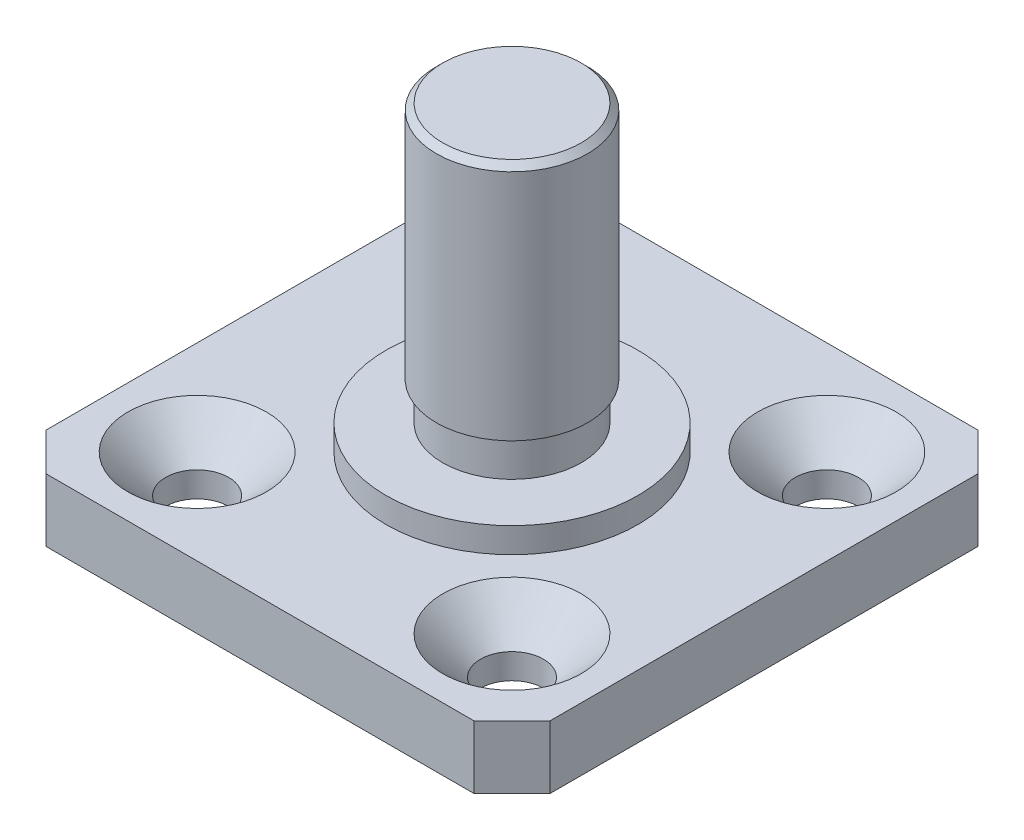
SolidWorks part; units mm, degrees
material "Литая углеродистая сталь"
ref_plane "Спереди" through (0, 0, 0) normal (0, 0, 1) x (1, 0, 0)
ref_plane "Сверху" through (0, 0, 0) normal (0, 1, 0) x (1, 0, 0)
ref_plane "Справа" through (0, 0, 0) normal (1, 0, 0) x (0, 0, -1)
sketch "Эскиз1" plane through (0, 0, 0) normal (0, 1, 0) x (1, 0, 0)
  line L1 (-20, -20) -> (20, -20)
  line L2 (-20, -20) -> (-20, 20)
  line L3 (-20, 20) -> (20, 20)
  line L4 (20, -20) -> (20, 20)
  line L5 (0, 20) -> (0, -20) construction
  line L6 (-20, 0) -> (20, 0) construction
  point P0 (0, 0)
  dimension "D1" = 40
extrude "Бобышка-Вытянуть1" add sketch "Эскиз1" along normal blind 5
chamfer "Фаска1" distance 3 angle 45 4 edges at (-20, 2.5, -20) (20, 2.5, -20) (-20, 2.5, 20) (20, 2.5, 20)
sketch "Эскиз2" plane through (0, 5, 0) normal (0, 1, 0) x (1, 0, 0)
  circle A0 centre (0, 0) radius 10
  dimension "D1" = 20
extrude "Бобышка-Вытянуть2" add sketch "Эскиз2" along normal blind 2
sketch "Эскиз3" plane through (0, 7, 0) normal (0, 1, 0) x (1, 0, 0)
  circle A0 centre (0, 0) radius 6
  dimension "D1" = 12
extrude "Бобышка-Вытянуть3" add sketch "Эскиз3" along normal blind 22
sketch "Эскиз4" plane through (0, 7, 0) normal (0, 1, 0) x (1, 0, 0)
  circle A0 centre (0, 0) radius 6 construction
  circle A1 centre (0, 0) radius 6
  circle A4 centre (0, 0) radius 5.5
  circle A5 centre (0, 0) radius 5.5
  dimension "D1" = 0.5
extrude "Вырез-Вытянуть1" cut sketch "Эскиз4" along normal blind 3
sketch "Эскиз5" plane through (0, 5, 0) normal (0, 1, 0) x (1, 0, 0)
  line L0 (0, 0) -> (0, 8.071) construction
  line L1 (0, 0) -> (4.4681, 0) construction
  circle A0 centre (-12.5, 12.5) radius 2.5
  circle A1 centre (12.5, 12.5) radius 2.5
  circle A2 centre (12.5, -12.5) radius 2.5
  circle A3 centre (-12.5, -12.5) radius 2.5
  dimension "D1" = 5
  dimension "D2" = 25
  dimension "D3" = 25
extrude "Вырез-Вытянуть2" cut sketch "Эскиз5" against normal through all
chamfer "Фаска2" distance 3 angle 45 4 edges at (-12.5, 5, 15) (12.5, 5, 15) (12.5, 5, -10) (-12.5, 5, -10)
chamfer "Фаска3" distance 0.5 angle 45 1 edges at (0, 29, 6)
